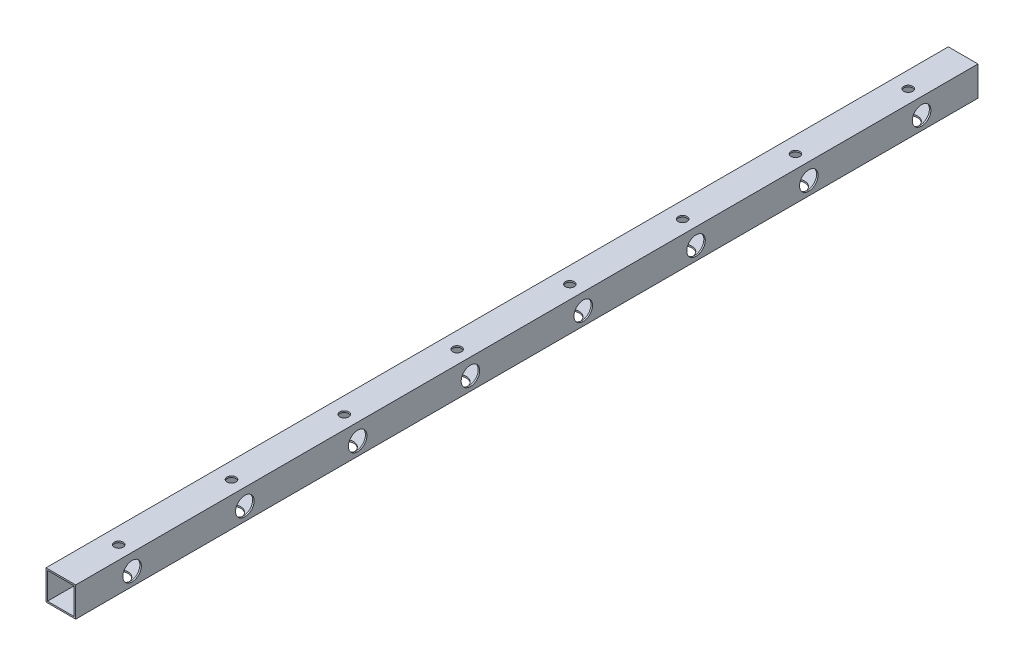
SolidWorks part; units mm, degrees
note: '?' marks a value the reader was unsure of.
material "Galvanized Steel"
ref_plane "Front Plane" through (0, 0, 0) normal (0, 0, 1) x (1, 0, 0)
ref_plane "Top Plane" through (0, 0, 0) normal (0, 1, 0) x (1, 0, 0)
ref_plane "Right Plane" through (0, 0, 0) normal (1, 0, 0) x (0, 0, -1)
sketch "Sketch1" plane through (0, 0, 0) normal (0, 0, 1) x (1, 0, 0)
  line L1 (20, -20) -> (-20, -20)
  line L2 (20, -20) -> (20, 20)
  line L3 (20, 20) -> (-20, 20)
  line L4 (-20, -20) -> (-20, 20)
  line L5 (20, -20) -> (-20, 20) construction
  line L6 (20, 20) -> (-20, -20) construction
  point P0 (0, 0)
  dimension "D1" = 40
  dimension "D2" = 40
extrude "Extrude-Thin1" add sketch "Sketch1" along normal blind 1216 thin thin type one direction reverse wall 2
sketch "Sketch2" plane through (-20, 0, 0) normal (-1, 0, 0) x (0, 0, 1)
  line L0 (1216, -20) -> (0, -20) construction
  line L1 (1216, 20) -> (1216, -20) construction
  circle A0 centre (1140, 0) radius 6
  dimension "D1" = 12
  dimension "D2" = 20
  dimension "D3" = 76
extrude "Boss-Extrude1" [suppressed] add sketch "Sketch2" against normal blind 12
sketch "Sketch3" [suppressed] plane through (-8, 0, 0) normal (1, 0, 0) x (0, 0, -1)
  circle A0 centre (-1140, 0) radius 3.5
  circle A3 centre (-1140, 0) radius 6 construction
  dimension "D1" = 7
extrude "Cut-Extrude1" [suppressed] cut sketch "Sketch3" against normal blind 20
cosmetic thread "Cosmetic Thread1" parameters "D2"=8
ref_axis "Axis1" through (0, 0, -91.2) along (0, 0, 1)?
pattern_circular "CirPattern1" [suppressed] count 2 every 90 about axis through (0, 0, -91.2) along (0, 0, 1)
pattern_linear "LPattern1" [suppressed] count 8 spacing 152
sketch "Sketch4" plane through (20, 0, 0) normal (1, 0, 0) x (0, 0, -1)
  line L0 (-1216, -20) -> (-1216, 20) construction
  line L1 (-1216, 20) -> (0, 20) construction
  circle A0 centre (-1140, -2) radius 12.5
  dimension "D2" = 22
  dimension "D3" = 25
  dimension "D1" = 76
extrude "Cut-Extrude2" cut sketch "Sketch4" against normal blind 10
sketch "Sketch5" plane through (0, -20, 0) normal (0, -1, 0) x (1, 0, 0)
  line L0 (-20, 1216) -> (20, 1216) construction
  line L1 (-20, 1216) -> (-20, 0) construction
  circle A0 centre (2, 1140) radius 12.5
  dimension "D1" = 25
  dimension "D2" = 76
  dimension "D3" = 22
extrude "Cut-Extrude3" cut sketch "Sketch5" against normal blind 10
sketch "Sketch6" plane through (-18, 0, 0) normal (1, 0, 0) x (0, 0, -1)
  line L0 (-1216, 20) -> (0, 20) construction
  circle A0 centre (-1140, -2) radius 6
  dimension "D1" = 12
  dimension "D2" = 22
extrude "Cut-Extrude4" cut sketch "Sketch6" against normal blind 10
sketch "Sketch7" plane through (0, 20, 0) normal (0, 1, 0) x (1, 0, 0)
  line L0 (20, -1216) -> (20, 0) construction
  circle A0 centre (2, -1140) radius 6
  dimension "D1" = 12
  dimension "D2" = 18
extrude "Cut-Extrude5" cut sketch "Sketch7" against normal blind 10
pattern_linear "LPattern2" count 8 spacing 152 along (0, 0, -1) of "Cut-Extrude2", "Cut-Extrude3", "Cut-Extrude5", "Cut-Extrude4"
